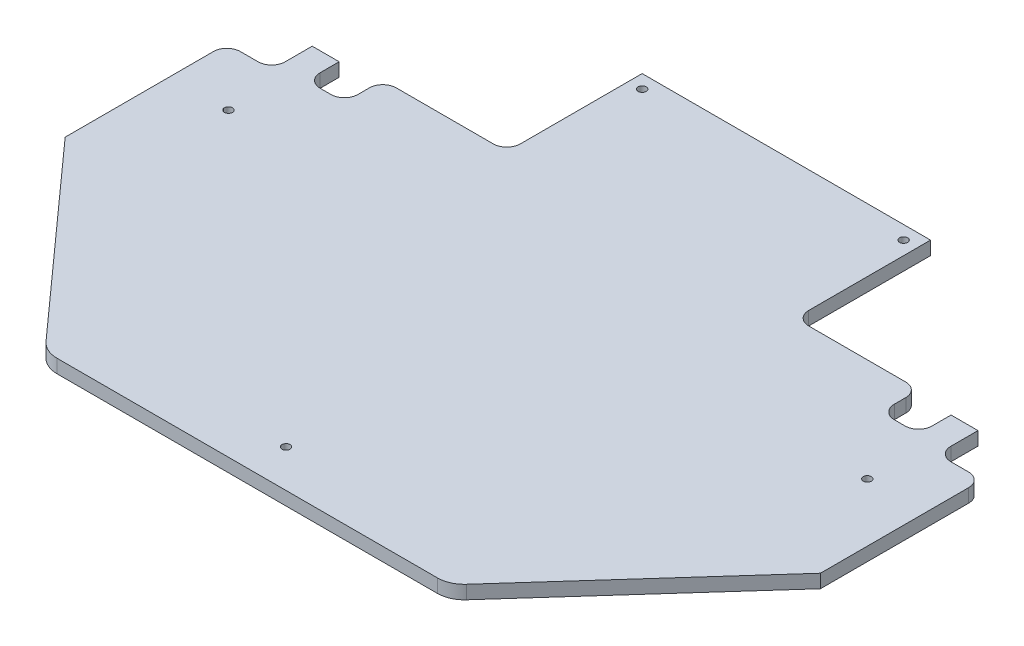
SolidWorks part; units mm, degrees
material "ABS PC"
ref_plane "Plan de face" through (0, 0, 0) normal (0, 0, 1) x (1, 0, 0)
ref_plane "Plan de dessus" through (0, 0, 0) normal (0, 1, 0) x (1, 0, 0)
ref_plane "Plan de droite" through (0, 0, 0) normal (1, 0, 0) x (0, 0, -1)
sketch "Esquisse1" plane through (0, 0, 0) normal (0, 1, 0) x (1, 0, 0)
  line L0 (-101.1, -245.0829) -> (-95, -245.0829) construction
  line L1 (-140.1, 31.2) -> (140.1, 31.2)
  line L2 (-140.1, 31.2) -> (-140.1, -245.0829)
  line L3 (-140.1, -245.0829) -> (140.1, -245.0829)
  line L4 (140.1, 31.2) -> (140.1, -245.0829)
  line L8 (-114.5, 31.2) -> (114.5, 31.2) construction
  line L9 (-140.1, 4) -> (-140.1, -4) construction
  line L10 (140.1, -4) -> (140.1, 4) construction
extrude "Boss.-Extru.1" add sketch "Esquisse1" along normal blind 5
sketch "Esquisse4" plane through (0, 5, 0) normal (0, 1, 0) x (1, 0, 0)
  line L0 (140.1, -245.0829) -> (101.1, -245.0829)
  line L1 (140.1, -245.0829) -> (140.1, -206.0829)
  line L2 (-101.1, -245.0829) -> (-140.1, -245.0829)
  line L3 (-140.1, -245.0829) -> (-140.1, -206.0829)
  arc A1 (101.1, -245.0829) -> (140.1, -206.0829) centre (101.1, -206.0829) ccw
  arc A3 (-140.1, -206.0829) -> (-101.1, -245.0829) centre (-101.1, -206.0829) ccw
  arc A4 (101.1, -245.0829) -> (140.1, -206.0829) centre (101.1, -206.0829) ccw construction
  arc A5 (-140.1, -206.0829) -> (-101.1, -245.0829) centre (-101.1, -206.0829) ccw construction
extrude "Enlèv. mat.-Extru.3" cut sketch "Esquisse4" against normal through all
sketch "Esquisse6" plane through (0, 5, 0) normal (0, 1, 0) x (1, 0, 0)
  line L0 (99.5, 0) -> (99.5, 26.9) construction
  line L1 (140.1, 31.2) -> (53.5, 31.2)
  line L2 (140.1, 31.2) -> (140.1, -41.25)
  line L3 (135.1, -36.25) -> (128.5, -36.25)
  line L4 (99.5, -24) -> (99.5, -28.25)
  line L5 (94.5, -19) -> (58.5, -19)
  line L6 (53.5, -14) -> (53.5, 31.2)
  line L9 (55.5, 15) -> (55.5, -15) construction
  line L10 (88, -16) -> (89, -16) construction
  line L11 (-53.5, -14) -> (-53.5, 31.2)
  line L12 (-94.5, -19) -> (-58.5, -19)
  line L13 (-99.5, -24) -> (-99.5, -28.25)
  line L14 (129.94, -36.25) -> (140.1, -36.25) construction
  line L15 (-135.1, -36.25) -> (-128.5, -36.25)
  line L16 (-140.1, 31.2) -> (-140.1, -41.25)
  line L17 (-140.1, 31.2) -> (-53.5, 31.2)
  line L18 (113.5, -28.25) -> (113.5, -21.2)
  line L19 (113.5, -21.2) -> (123.5, -21.2)
  line L20 (123.5, -21.2) -> (123.5, -31.25)
  line L21 (108.5, -33.25) -> (104.5, -33.25)
  line L22 (-123.5, -21.2) -> (-123.5, -31.25)
  line L23 (-113.5, -21.2) -> (-123.5, -21.2)
  line L24 (-113.5, -28.25) -> (-113.5, -21.2)
  line L25 (0, 0) -> (0, 86.4947) construction
  line L26 (-108.5, -33.25) -> (-104.5, -33.25)
  line L27 (140.1, 36.25) -> (140.1, -245.0829) construction
  arc A0 (140.1, -41.25) -> (135.1, -36.25) centre (135.1, -41.25) ccw
  arc A1 (-99.5, -24) -> (-94.5, -19) centre (-94.5, -24) cw
  arc A2 (58.5, -19) -> (53.5, -14) centre (58.5, -14) cw
  arc A3 (-104.5, -33.25) -> (-99.5, -28.25) centre (-104.5, -28.25) ccw
  arc A4 (104.5, -33.25) -> (99.5, -28.25) centre (104.5, -28.25) cw
  arc A5 (99.5, -24) -> (94.5, -19) centre (94.5, -24) ccw
  arc A6 (-58.5, -19) -> (-53.5, -14) centre (-58.5, -14) ccw
  arc A7 (-140.1, -41.25) -> (-135.1, -36.25) centre (-135.1, -41.25) cw
  arc A8 (113.5, -28.25) -> (108.5, -33.25) centre (108.5, -28.25) cw
  arc A9 (123.5, -31.25) -> (128.5, -36.25) centre (128.5, -31.25) ccw
  arc A10 (-123.5, -31.25) -> (-128.5, -36.25) centre (-128.5, -31.25) cw
  arc A11 (-113.5, -28.25) -> (-108.5, -33.25) centre (-108.5, -28.25) ccw
  point P19 (0, 0)
  point P20 (0, 0)
  point P23 (53.5, 26.6714)
  point P28 (0, 0)
  point P41 (99.5, -36.25)
  point P43 (99.5, -19)
  point P49 (0, 21.2)
  point P50 (-53.5, 31.0989)
  point P58 (113.5, -33.25)
  dimension "D1" = 5
  dimension "D4" = 3
  dimension "D2" = 2
  dimension "D3" = 3
extrude "Enlèv. mat.-Extru.5" cut sketch "Esquisse6" against normal through all
sketch "Esquisse8" plane through (0, 0, 0) normal (0, -1, 0) x (1, 0, 0)
  line L2 (0, 0) -> (0, -63.4963) construction
  line L4 (53.5, -31.2) -> (53.5, 14) construction
  line L5 (53.5, -31.2) -> (-53.5, -31.2) construction
  line L6 (-53.5, 14) -> (-53.5, -31.2) construction
  circle A0 centre (-48.5, -26.2) radius 1.5
  circle A1 centre (48.5, -26.2) radius 1.5
  dimension "D1" = 3
  dimension "D4" = 5
  dimension "D2" = 3
  dimension "D3" = 5
  dimension "D5" = 5
  dimension "D6" = 5
extrude "Enlèv. mat.-Extru.8" cut sketch "Esquisse8" against normal through all
sketch "Esquisse10" plane through (0, 5, 0) normal (0, 1, 0) x (1, 0, 0)
  line L0 (118.5, -57.265) -> (123.5, -57.265) construction
  line L1 (123.5, -55.765) -> (123.5, -58.765) construction
  line L2 (-123.5, -57.265) -> (-118.5, -57.265) construction
  line L3 (-123.5, -58.765) -> (-123.5, -55.765) construction
  circle A0 centre (118.5, -57.265) radius 1.5
  circle A1 centre (-118.5, -57.265) radius 1.5
  dimension "D2" = 3
  dimension "D1" = 5
extrude "Enlèv. mat.-Extru.11" cut sketch "Esquisse10" against normal through all
sketch "Esquisse12" plane through (0, 5, 0) normal (0, 1, 0) x (1, 0, 0)
  line L0 (-140.1, -96.25) -> (-75, -168.8)
  line L3 (-75, -168.8) -> (75, -168.8)
  line L4 (75, -168.8) -> (140.1, -96.25)
  line L5 (140.1, -206.0829) -> (140.1, -41.25) construction
  line L6 (-140.1, -41.25) -> (-140.1, -206.0829) construction
  line L9 (-140.1, -96.25) -> (-140.1, -294.9836)
  line L10 (-140.1, -294.9836) -> (146.0328, -294.9836)
  line L11 (146.0328, -294.9836) -> (140.1, -96.25)
  line L12 (128.5, -36.25) -> (135.1, -36.25) construction
  line L13 (-135.1, -36.25) -> (-128.5, -36.25) construction
  line L14 (53.5, 31.2) -> (-53.5, 31.2) construction
  dimension "D1" = 60
  dimension "D2" = 60
  dimension "D3" = 200
  dimension "D4" = 150
  dimension "D5" = 65.1
extrude "Enlèv. mat.-Extru.15" cut sketch "Esquisse12" against normal through all
fillet "Congé1" radius 10 2 edges at (-75, 2.5, 168.8) (75, 2.5, 168.8)
sketch "Esquisse13" plane through (0, 5, 0) normal (0, 1, 0) x (1, 0, 0)
  line L0 (70.5375, -168.8) -> (-70.5375, -168.8) construction
  circle A0 centre (0.3874, -154.8) radius 1.5
  arc A1 (-77.9803, -165.4786) -> (-70.5375, -168.8) centre (-70.5375, -158.8) ccw construction
  point P9 (-74.6126, -167.932)
  dimension "D2" = 75
  dimension "D3" = 3
  dimension "D1" = 14
extrude "Enlèv. mat.-Extru.16" cut sketch "Esquisse13" against normal through all
